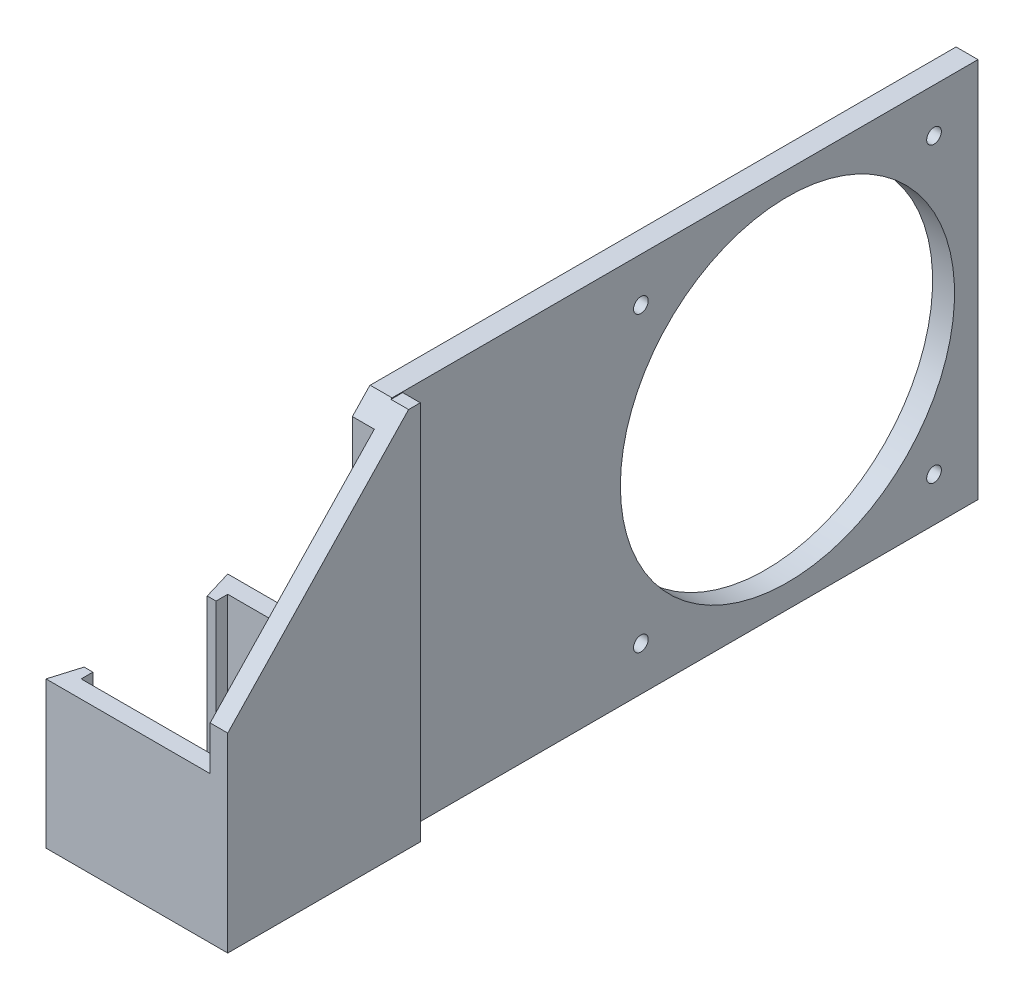
SolidWorks part; units mm, degrees
ref_plane "Спереди" through (0, 0, 0) normal (0, 0, 1) x (1, 0, 0)
ref_plane "Сверху" through (0, 0, 0) normal (0, 1, 0) x (1, 0, 0)
ref_plane "Справа" through (0, 0, 0) normal (1, 0, 0) x (0, 0, -1)
sketch "Эскиз1" plane through (0, 0, 0) normal (0, 1, 0) x (1, 0, 0)
  line L0 (-66.8258, 34.9697) -> (-66.8258, 29.9697)
  line L1 (-63.8258, 29.9697) -> (-63.8258, 31.9697)
  line L2 (-63.8258, 31.9697) -> (-38.8258, 31.9697)
  line L3 (-38.8258, 31.9697) -> (-38.8258, 6.9697)
  line L4 (-38.8258, 6.9697) -> (-63.8258, 6.9697)
  line L5 (-63.8258, 6.9697) -> (-63.8258, 8.9697)
  line L6 (-63.8258, 8.9697) -> (-66.8258, 8.9697)
  line L7 (-66.8258, 8.9697) -> (-66.8258, 3.9697)
  line L8 (-66.8258, 3.9697) -> (-22.1235, 3.9697)
  line L9 (-22.1235, 3.9697) -> (-36.579, 34.9697)
  line L10 (-36.579, 34.9697) -> (-66.8258, 34.9697)
  line L11 (-66.8258, 29.9697) -> (-63.8258, 29.9697)
  dimension "D1" = 25
  dimension "D2" = 25
  dimension "D3" = 25
  dimension "D4" = 155
  dimension "D5" = 3
  dimension "D6" = 3
  dimension "D7" = 3
  dimension "D8" = 3
  dimension "D9" = 2
  dimension "D10" = 2
extrude "Бобышка-Вытянуть1" add sketch "Эскиз1" along normal blind 25
sketch "Эскиз3" plane through (0, 0, 0) normal (0, -1, 0) x (1, 0, 0)
  line L0 (-66.8258, -3.9697) -> (-65.3258, -8.9697)
  line L1 (-63.8258, -8.9697) -> (-66.8258, -8.9697) construction
  line L2 (-65.3258, -8.9697) -> (-66.8258, -8.9697)
  line L3 (-66.8258, -8.9697) -> (-66.8258, -3.9697)
  line L4 (-66.8258, -29.9697) -> (-66.8258, -34.9697)
  line L5 (-66.8258, -34.9697) -> (-65.3258, -29.9697)
  line L6 (-66.8258, -29.9697) -> (-63.8258, -29.9697) construction
  line L7 (-65.3258, -29.9697) -> (-66.8258, -29.9697)
extrude "Вырез-Вытянуть4" cut sketch "Эскиз3" against normal through all
sketch "Эскиз7" plane through (0, 0, 0) normal (0, -1, 0) x (-1, 0, 0)
  line L1 (36.0076, 1.3029) -> (19.3993, 1.3029)
  line L2 (36.0076, 1.3029) -> (36.0076, 39.7765)
  line L3 (36.0076, 39.7765) -> (19.3993, 39.7765)
  line L4 (19.3993, 1.3029) -> (19.3993, 39.7765)
extrude "Вырез-Вытянуть14" cut sketch "Эскиз7" against normal through all
sketch "Эскиз8" plane through (0, 0, 0) normal (0, -1, 0) x (-1, 0, 0)
  line L0 (66.8258, 3.9697) -> (36.0076, 3.9697) construction
  line L1 (38.7989, 3.9697) -> (33.7989, 3.9697)
  line L2 (38.7989, 3.9697) -> (38.7989, 34.9383)
  line L3 (38.7989, 34.9383) -> (33.7989, 34.9383)
  line L4 (33.7989, 3.9697) -> (33.7989, 34.9383)
  dimension "D1" = 5
extrude "Бобышка-Вытянуть2" add sketch "Эскиз8" against normal up to surface (25 mm away) up to face at (-54.2963, 25, -20.5678)
sketch "Эскиз9" plane through (0, 0, -34.9383) normal (0, 0, -1) x (-1, 0, 0)
  line L0 (36.5643, 0) -> (33.7989, 0) construction
  line L1 (36.7989, 0) -> (39.5643, 0)
  line L2 (36.7989, 0) -> (36.7989, 65)
  line L3 (36.7989, 65) -> (39.5643, 65)
  line L4 (39.5643, 0) -> (39.5643, 65)
  line L5 (33.7989, 25) -> (33.7989, 0) construction
  line L6 (36.5643, 25) -> (36.5643, 0) construction
  dimension "D1" = 3
  dimension "D2" = 3
  dimension "D3" = 65
extrude "Бобышка-Вытянуть3" add sketch "Эскиз9" along normal blind 100
sketch "Эскиз10" plane through (0, 25, 0) normal (0, 1, 0) x (1, 0, 0)
  line L0 (-66.8258, 3.9697) -> (-33.7989, 3.9697) construction
  line L1 (-33.7989, 34.9383) -> (-38.8258, 34.9383)
  line L2 (-33.7989, 34.9383) -> (-33.7989, 3.9697)
  line L3 (-33.7989, 3.9697) -> (-38.8258, 3.9697)
  line L4 (-38.8258, 34.9383) -> (-38.8258, 3.9697)
extrude "Бобышка-Вытянуть4" add sketch "Эскиз10" along normal up to surface (40 mm away) up to face at (-38.1816, 65, -84.9383)
sketch "Эскиз11" plane through (-33.7989, 0, 0) normal (1, 0, 0) x (0, 0, -1)
  line L0 (34.9383, 65) -> (3.9697, 32.5) construction
  line L1 (3.9697, 65) -> (3.9697, 0) construction
  line L2 (34.9383, 65) -> (3.9697, 32.5)
  line L3 (3.9697, 32.5) -> (3.9697, 65)
  line L4 (3.9697, 65) -> (34.9383, 65)
extrude "Вырез-Вытянуть15" cut sketch "Эскиз11" against normal blind 100
sketch "Эскиз12" plane through (-36.7989, 0, 0) normal (1, 0, 0) x (0, 0, -1)
  line L0 (69.9383, 65) -> (69.9383, 0) construction
  line L1 (134.9383, 65) -> (34.9383, 65) construction
  line L2 (134.9383, 0) -> (34.9697, 0) construction
  line L3 (134.9383, 65) -> (134.9383, 0) construction
  line L4 (69.9383, 0) -> (134.9383, 65) construction
  circle A0 centre (102.4383, 32.5) radius 28.5
  dimension "D1" = 65
extrude "Вырез-Вытянуть16" cut sketch "Эскиз12" against normal blind 100
sketch "Эскиз13" plane through (-36.7989, 0, 0) normal (1, 0, 0) x (0, 0, -1)
  line L0 (134.9383, 32.5) -> (61.5486, 32.5) construction
  line L1 (134.9383, 65) -> (134.9383, 0) construction
  line L2 (102.4383, 32.5) -> (102.4383, 61) construction
  line L3 (102.4383, 61) -> (102.4383, 4) construction
  line L4 (65.365, 57.5) -> (138.8305, 57.5) construction
  line L5 (127.4383, 65) -> (127.4383, -8.7306) construction
  line L6 (134.9383, 65) -> (34.9383, 65) construction
  line L7 (62.5027, 7.5) -> (133.2422, 7.5) construction
  line L8 (77.4383, 65) -> (77.4383, 0) construction
  line L9 (134.9383, 0) -> (34.9697, 0) construction
  circle A0 centre (102.4383, 32.5) radius 28.5 construction
  circle A1 centre (77.4383, 57.5) radius 1.25
  circle A2 centre (127.4383, 57.5) radius 1.25
  circle A3 centre (127.4383, 7.5) radius 1.25
  circle A4 centre (77.4383, 7.5) radius 1.25
  dimension "D1" = 25
  dimension "D2" = 25
  dimension "D3" = 25
  dimension "D4" = 25
extrude "Вырез-Вытянуть17" cut sketch "Эскиз13" against normal blind 100
sketch "Эскиз14" plane through (0, 0, 0) normal (0, -1, 0) x (-1, 0, 0)
  line L0 (38.8258, 31.9697) -> (38.8258, 134.9383) construction
  line L1 (36.7989, 134.9383) -> (39.5643, 134.9383) construction
  line L2 (33.7989, 34.9383) -> (33.7989, 3.9697) construction
  line L3 (33.7989, 34.8135) -> (38.8258, 34.8135)
  line L4 (33.7989, 34.8135) -> (33.7989, 134.9383)
  line L5 (33.7989, 134.9383) -> (38.8258, 134.9383)
  line L6 (38.8258, 34.8135) -> (38.8258, 134.9383)
extrude "Вырез-Вытянуть19" cut sketch "Эскиз14" against normal through all
sketch "Эскиз15" plane through (0, 0, 0) normal (0, -1, 0) x (1, 0, 0)
  line L0 (-33.7989, -34.8135) -> (-38.8258, -34.8135) construction
  line L1 (-33.7989, -3.9697) -> (-35.8258, -3.9697)
  line L2 (-33.7989, -3.9697) -> (-33.7989, -34.8135)
  line L3 (-33.7989, -34.8135) -> (-35.8258, -34.8135)
  line L4 (-35.8258, -3.9697) -> (-35.8258, -34.8135)
  line L5 (-38.8258, -31.9697) -> (-38.8258, -6.9697) construction
  dimension "D1" = 3
extrude "Вырез-Вытянуть20" cut sketch "Эскиз15" against normal through all
sketch "Эскиз16" plane through (-39.5643, 0, 0) normal (-1, 0, 0) x (0, 0, 1)
  line L1 (-134.9383, 65) -> (-34.9697, 65)
  line L2 (-134.9383, 65) -> (-134.9383, 0)
  line L3 (-134.9383, 0) -> (-34.9697, 0)
  line L4 (-34.9697, 65) -> (-34.9697, 0)
  circle A0 centre (-102.4383, 32.5) radius 28.5
  circle A1 centre (-127.4383, 57.5) radius 1.25
  circle A2 centre (-77.4383, 57.5) radius 1.25
  circle A3 centre (-77.4383, 7.5) radius 1.25
  circle A4 centre (-127.4383, 7.5) radius 1.25
extrude "Бобышка-Вытянуть5" add sketch "Эскиз16" along normal blind 3
sketch "Эскиз17" plane through (0, 25, 0) normal (0, 1, 0) x (1, 0, 0)
  line L1 (-42.5643, 34.9697) -> (-38.8258, 34.9697)
  line L2 (-42.5643, 34.9697) -> (-42.5643, 31.9697)
  line L3 (-42.5643, 31.9697) -> (-38.8258, 31.9697)
  line L4 (-38.8258, 34.9697) -> (-38.8258, 31.9697)
extrude "Бобышка-Вытянуть7" add sketch "Эскиз17" along normal up to surface (40.033 mm away) up to face at (-37.3258, 48.6845, -19.3916)
chamfer "Фаска1" distance 10 angle 45 1 edges at (-42.5643, 12.5, -34.9697)
sketch "Эскиз18" plane through (0, 0, -34.8135) normal (0, 0, -1) x (-1, 0, 0)
  line L1 (35.8258, 64.869) -> (38.8258, 64.869)
  line L2 (35.8258, 64.869) -> (35.8258, 0)
  line L3 (35.8258, 0) -> (38.8258, 0)
  line L4 (38.8258, 64.869) -> (38.8258, 0)
extrude "Бобышка-Вытянуть8" add sketch "Эскиз18" along normal blind 2
